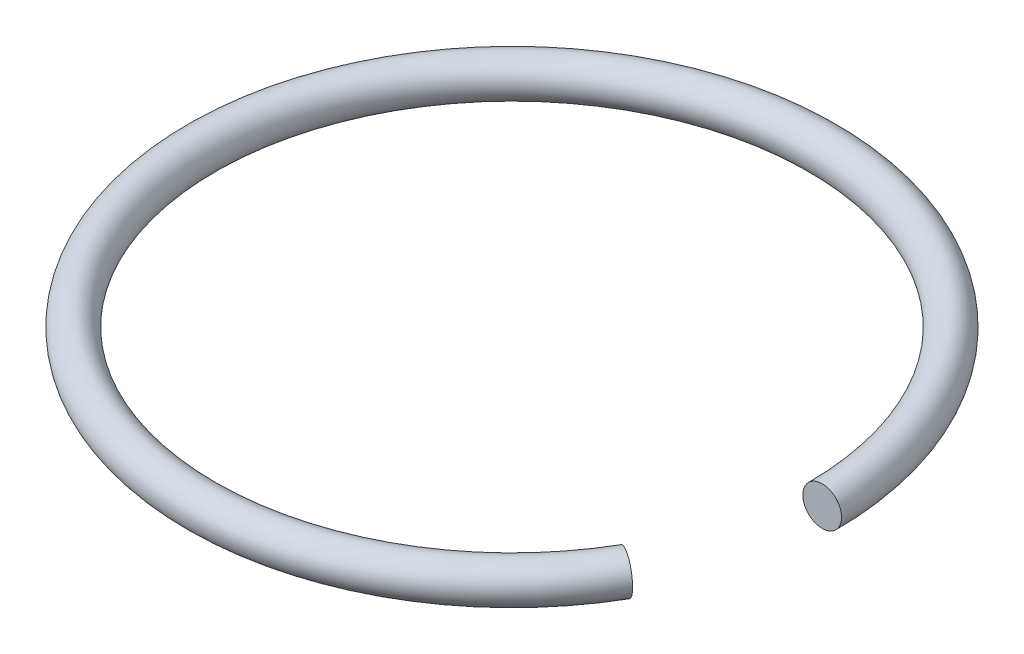
SolidWorks part; units mm, degrees
material "Alloy Steel"
ref_plane "Front Plane" through (0, 0, 0) normal (0, 0, 1) x (1, 0, 0)
ref_plane "Top Plane" through (0, 0, 0) normal (0, 1, 0) x (1, 0, 0)
ref_plane "Right Plane" through (0, 0, 0) normal (1, 0, 0) x (0, 0, -1)
sketch "Sketch1" plane through (0, 0, 0) normal (0, 0, 1) x (1, 0, 0)
  line L0 (0, 0) -> (0, 85.2237) construction
  circle A0 centre (8, 0) radius 0.5
  dimension "D2" = 1
  dimension "D1" = 16
revolve "Revolve1" add sketch "Sketch1" angle 330 about L0
ref_axis "Axis1" through (0, 13.6226, 0) along (0, -1, 0)
